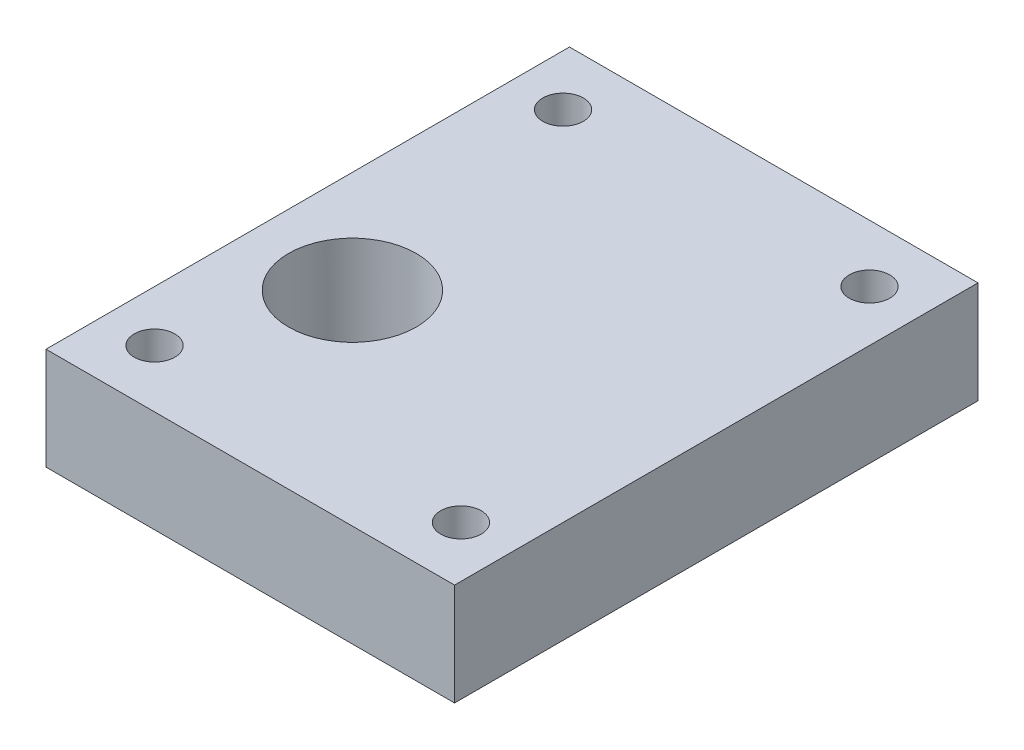
SolidWorks part; units mm, degrees
material "6061 Alloy"
ref_plane "Front" through (0, 0, 0) normal (0, 0, 1) x (1, 0, 0)
ref_plane "Top" through (0, 0, 0) normal (0, 1, 0) x (1, 0, 0)
ref_plane "Right" through (0, 0, 0) normal (1, 0, 0) x (0, 0, -1)
sketch "Sketch1" plane through (0, 0, 0) normal (0, 1, 0) x (1, 0, 0)
  line L1 (-50.8, -65.0875) -> (50.8, -65.0875)
  line L2 (-50.8, -65.0875) -> (-50.8, 65.0875)
  line L3 (-50.8, 65.0875) -> (50.8, 65.0875)
  line L4 (50.8, -65.0875) -> (50.8, 65.0875)
  line L5 (-50.8, -65.0875) -> (50.8, 65.0875) construction
  line L6 (-50.8, 65.0875) -> (50.8, -65.0875) construction
  point P0 (0, 0)
  dimension "D1" = 101.6
  dimension "D2" = 130.175
extrude "Boss-Extrude1" add sketch "Sketch1" along normal mid plane 25.4
sketch "Sketch2" plane through (0, 12.7, 0) normal (0, 1, 0) x (1, 0, 0)
  line L1 (-50.8, 65.0875) -> (-50.8, -65.0875) construction
  line L2 (-50.8, -65.0875) -> (50.8, -65.0875) construction
  circle A0 centre (-25.4, -14.2875) radius 15.875
  point P6 (0, 0)
  dimension "D2" = 31.75
  dimension "D1" = 25.4
  dimension "D3" = 50.8
extrude "Cut-Extrude1" cut sketch "Sketch2" against normal through all both and the other way through all
sketch "Sketch3" plane through (0, -12.7, 0) normal (0, -1, 0) x (1, 0, 0)
  point P0 (-38.1, 50.8)
  point P1 (38.1, 50.8)
  point P3 (38.1, -50.8)
  point P5 (-38.1, -50.8)
hole_wizard "3/8 Clearance Hole1" positions "Sketch4" profile "Sketch5" hole size "3/8" standard "ANSI Inch" end condition up to next
sketch "Sketch4" plane through (0, -12.7, 0) normal (0, -1, 0) x (-1, 0, 0)
  point P0 (-38.1, 50.8)
  point P3 (38.1, 50.8)
  point P6 (38.1, -50.8)
  point P9 (-38.1, -50.8)
sketch "Sketch5" plane through (38.1, -12.7, -50.8) normal (1, 0, 0) x (0, 0, -1)
  line L0 (0, 0) -> (0, 25.4)
  line L1 (0, 25.4) -> (5.0419, 25.4)
  line L2 (5.0419, 25.4) -> (5.0419, 0)
  line L5 (5.0419, 0) -> (0, 0)
  line L11 (0, -6.35) -> (0, 107.95) construction
  dimension "Thru Hole Dia." = 10.0838
  dimension "Thru Hole Depth" = 25.4
